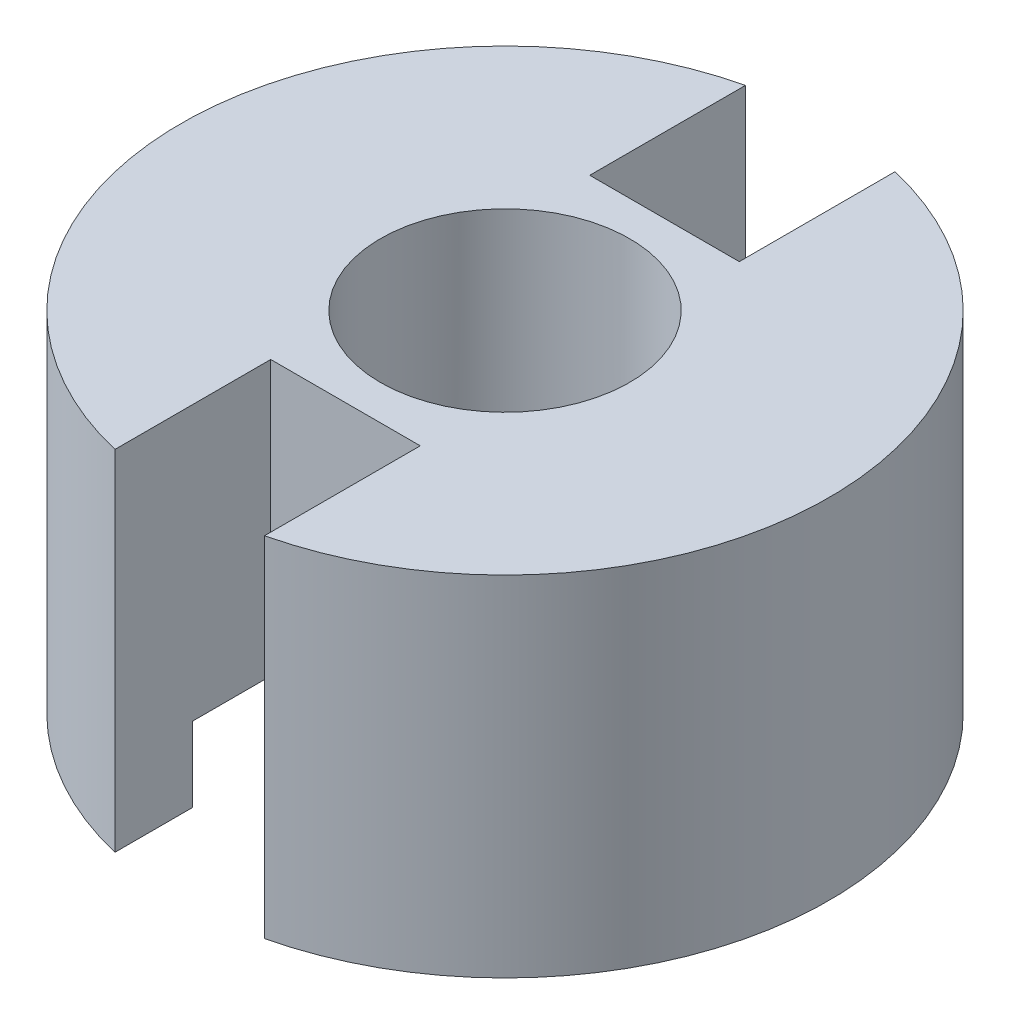
SolidWorks part; units mm, degrees
ref_plane "Front Plane" through (0, 0, 0) normal (0, 0, 1) x (1, 0, 0)
ref_plane "Top Plane" through (0, 0, 0) normal (0, 1, 0) x (1, 0, 0)
ref_plane "Right Plane" through (0, 0, 0) normal (1, 0, 0) x (0, 0, -1)
sketch "Sketch1" plane through (0, 0, 0) normal (0, 1, 0) x (1, 0, 0)
  circle A0 centre (0, 0) radius 6.5
  dimension "D1" = 13
extrude "Boss-Extrude1" add sketch "Sketch1" along normal blind 7
sketch "Sketch2" plane through (0, 0, 0) normal (0, -1, 0) x (1, 0, 0)
  circle A0 centre (0, 0) radius 5
  circle A1 centre (0, 0) radius 6.5 construction
  dimension "D1" = 1.5
extrude "Cut-Extrude1" cut sketch "Sketch2" against normal blind 1.5
sketch "Sketch3" plane through (0, 7, 0) normal (0, 1, 0) x (1, 0, 0)
  line L1 (-1.5, 6.7) -> (1.5, 6.7)
  line L2 (-1.5, 6.7) -> (-1.5, 3.2)
  line L3 (-1.5, 3.2) -> (1.5, 3.2)
  line L4 (1.5, 6.7) -> (1.5, 3.2)
  line L5 (-1.5, -3.2) -> (1.5, -3.2)
  line L6 (-1.5, -3.2) -> (-1.5, -6.7)
  line L7 (-1.5, -6.7) -> (1.5, -6.7)
  line L8 (1.5, -3.2) -> (1.5, -6.7)
  circle A0 centre (0, 0) radius 2.5
  dimension "D1" = 5
  dimension "D3" = 3.2
  dimension "D2" = 3.2
  dimension "D4" = 3
  dimension "D5" = 1.5
  dimension "D6" = 1.5
  dimension "D7" = 1.5
  dimension "D8" = 3.5
  dimension "D9" = 3.5
extrude "Cut-Extrude2" cut sketch "Sketch3" against normal through all
sketch "Sketch4" plane through (0, 1.5, 0) normal (0, -1, 0) x (1, 0, 0)
  line L0 (-1.5, 2) -> (-1.5, 3.2)
  line L1 (-1.5, 3.2) -> (1.5, 3.2)
  line L2 (1.5, 3.2) -> (1.5, 2)
  line L3 (-1.5, -2) -> (-1.5, -3.2)
  line L4 (-1.5, -3.2) -> (1.5, -3.2)
  line L5 (1.5, -3.2) -> (1.5, -2)
  arc A0 (-1.5, -2) -> (1.5, -2) centre (0, 0) ccw
  arc A1 (1.5, 2) -> (-1.5, 2) centre (0, 0) ccw
  dimension "D1" = 5
extrude "Boss-Extrude2" add sketch "Sketch4" along normal blind 1.5
